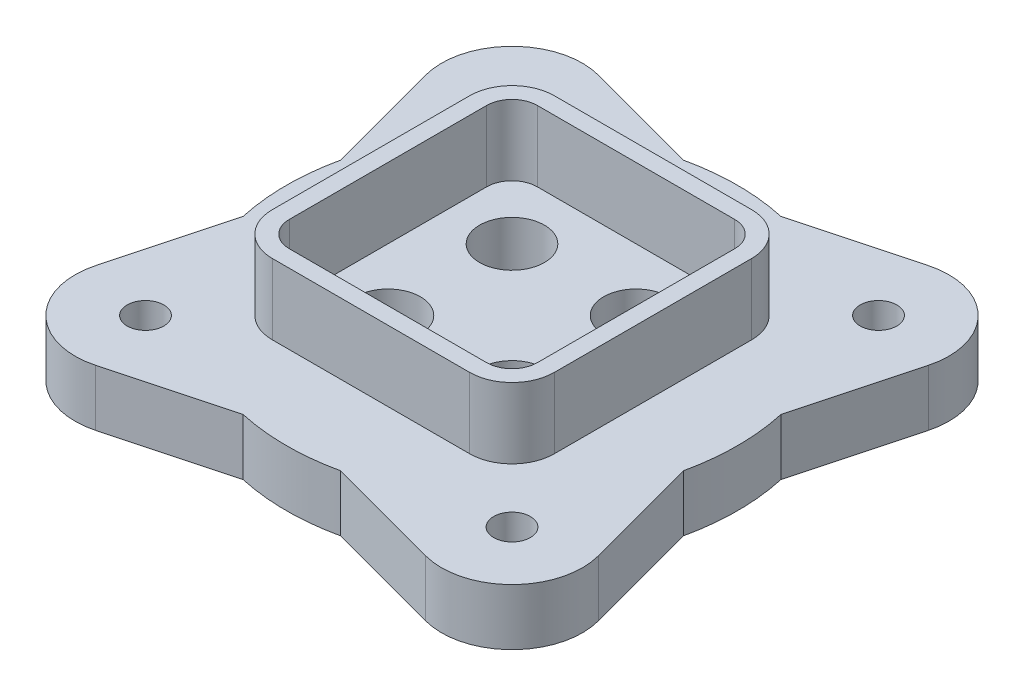
SolidWorks part; units mm, degrees
ref_plane "Front Plane" through (0, 0, 0) normal (0, 0, 1) x (1, 0, 0)
ref_plane "Top Plane" through (0, 0, 0) normal (0, 1, 0) x (1, 0, 0)
ref_plane "Right Plane" through (0, 0, 0) normal (1, 0, 0) x (0, 0, -1)
sketch "Sketch1" plane through (0, 0, 0) normal (0, 1, 0) x (1, 0, 0)
  line L0 (0, 80) -> (0, -95.0123) construction
  line L1 (104.2925, 0) -> (-100.8351, 0) construction
  line L2 (17.3129, 78.1042) -> (58.5295, 89.1481)
  line L3 (-35, -50) -> (35, -50)
  line L4 (-50, -35) -> (-50, 35)
  line L5 (-35, 50) -> (35, 50)
  line L6 (50, -35) -> (50, 35)
  line L7 (-50, -50) -> (50, 50) construction
  line L8 (-50, 50) -> (50, -50) construction
  line L9 (89.1481, 58.5295) -> (78.1042, 17.3129)
  line L10 (0, 0) -> (89.7627, 89.7627) construction
  line L11 (0, 0) -> (-89.7627, 89.7627) construction
  line L12 (-89.1481, 58.5295) -> (-78.1042, 17.3129)
  line L13 (-17.3129, 78.1042) -> (-58.5295, 89.1481)
  line L14 (-17.3129, -78.1042) -> (-58.5295, -89.1481)
  line L15 (-89.1481, -58.5295) -> (-78.1042, -17.3129)
  line L16 (89.1481, -58.5295) -> (78.1042, -17.3129)
  line L17 (17.3129, -78.1042) -> (58.5295, -89.1481)
  line L18 (-35, 44) -> (35, 44)
  line L19 (44, -35) -> (44, 35)
  line L20 (-35, -44) -> (35, -44)
  line L21 (-44, -35) -> (-44, 35)
  circle A0 centre (22, 22) radius 11.5
  circle A1 centre (65, 65) radius 6.5
  arc A2 (78.1042, -17.3129) -> (78.1042, 17.3129) centre (0, 0) ccw
  arc A3 (89.1481, 58.5295) -> (58.5295, 89.1481) centre (65, 65) ccw
  arc A4 (-89.1481, 58.5295) -> (-58.5295, 89.1481) centre (-65, 65) cw
  arc A5 (17.3129, 78.1042) -> (-17.3129, 78.1042) centre (0, 0) ccw
  arc A6 (-78.1042, -17.3129) -> (-78.1042, 17.3129) centre (0, 0) cw
  circle A7 centre (-65, 65) radius 6.5
  circle A8 centre (-65, -65) radius 6.5
  arc A9 (17.3129, -78.1042) -> (-17.3129, -78.1042) centre (0, 0) cw
  arc A10 (-89.1481, -58.5295) -> (-58.5295, -89.1481) centre (-65, -65) ccw
  arc A11 (89.1481, -58.5295) -> (58.5295, -89.1481) centre (65, -65) cw
  circle A12 centre (65, -65) radius 6.5
  arc A13 (35, -50) -> (50, -35) centre (35, -35) ccw
  arc A14 (-35, -50) -> (-50, -35) centre (-35, -35) cw
  arc A15 (-50, 35) -> (-35, 50) centre (-35, 35) cw
  arc A16 (35, 50) -> (50, 35) centre (35, 35) cw
  arc A17 (35, 44) -> (44, 35) centre (35, 35) cw
  arc A18 (35, -44) -> (44, -35) centre (35, -35) ccw
  arc A19 (-35, -44) -> (-44, -35) centre (-35, -35) cw
  arc A20 (-44, 35) -> (-35, 44) centre (-35, 35) cw
  circle A21 centre (-22, 22) radius 11.5
  circle A22 centre (-22, -22) radius 11.5
  circle A23 centre (22, -22) radius 11.5
  point P7 (0, 0)
  point P12 (0, 80)
  point P15 (23.6275, 80)
  point P19 (0, 0)
  dimension "D1" = 50
  dimension "D2" = 23
  dimension "D6" = 13
  dimension "D9" = 160
  dimension "D10" = 15
  dimension "D3" = 100
  dimension "D4" = 100
  dimension "D5" = 22
  dimension "D7" = 65
  dimension "D8" = 60
  dimension "D11" = 6
extrude "Boss-Extrude1" add sketch "Sketch1" along normal blind 20 contours A20 L21 A19 L20 A18 L19 A17 L18 A21 A0 A22 A23 | A11 L16 A2 L9 A3 L2 A5 L13 A4 L12 A6 L15 A10 L14 A9 L17 A12 A8 A1 A7 L5 A16 L6 A13 L3 A14 L4 A15 region at (38.5801, 0, -81.1673) region at (0, 0, 0)
extrude "Boss-Extrude2" add sketch "Sketch1<3>" along normal blind 45 contours A16 L5 A15 L4 A14 L3 A13 L6 L21 A20 L18 A17 L19 A18 L20 A19 region at (-44.6066, 0, 44.6066)
sketch "Sketch1<3>" plane through (0, 0, 0) normal (0, 1, 0) x (1, 0, 0) same geometry as "Sketch1"
sketch "Sketch2" plane through (0, 0, 0) normal (0, -1, 0) x (1, 0, 0)
  circle A0 centre (0, 0) radius 72.5
  circle A1 centre (0, 0) radius 52.5
  dimension "D1" = 145
  dimension "D2" = 105
extrude "Cut-Extrude1" cut sketch "Sketch2" against normal blind 3
